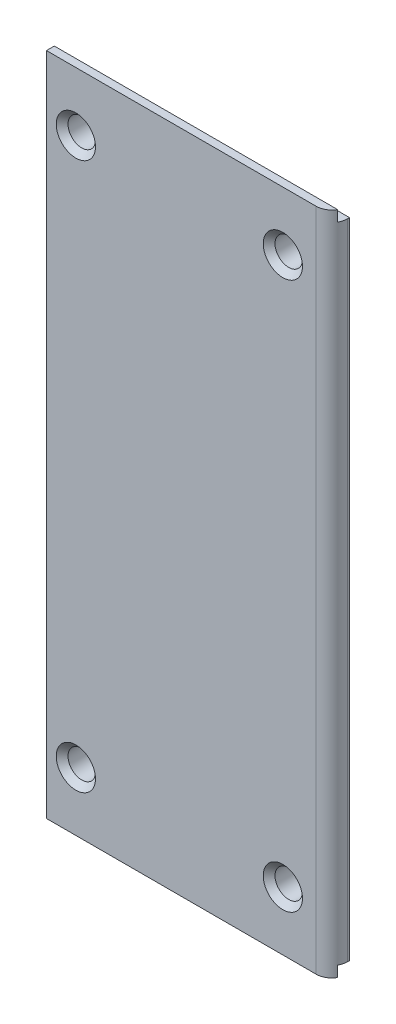
SolidWorks part; units mm, degrees
ref_plane "Спереди" through (0, 0, 0) normal (0, 0, 1) x (1, 0, 0)
ref_plane "Сверху" through (0, 0, 0) normal (0, 1, 0) x (1, 0, 0)
ref_plane "Справа" through (0, 0, 0) normal (1, 0, 0) x (0, 0, -1)
sketch "Эскиз1" plane through (0, 0, 0) normal (0, 0, 1) x (1, 0, 0)
  line L0 (-14.55, 33) -> (14.55, 33)
  line L1 (14.55, 33) -> (14.55, 34.1)
  line L2 (14.55, 34.1) -> (-14.55, 34.1)
  line L3 (-14.55, 34.1) -> (-14.55, 33)
  line L4 (14.55, -33) -> (-14.55, -33)
  line L5 (-14.55, -33) -> (-14.55, -34.1)
  line L6 (-14.55, -34.1) -> (14.55, -34.1)
  line L7 (14.55, -34.1) -> (14.55, -33)
sketch "Эскиз2" plane through (0, 0, 0) normal (0, 0, 1) x (1, 0, 0)
  line L0 (-14.55, 34.1) -> (-14.55, 33) construction
  line L1 (-14.55, 33.9) -> (14.55, 33.9)
  line L2 (-14.55, 33.9) -> (-14.55, -33.9)
  line L3 (-14.55, -33.9) -> (14.55, -33.9)
  line L4 (14.55, 33.9) -> (14.55, -33.9)
  line L5 (14.55, -34.1) -> (14.55, -33) construction
  line L6 (-14.55, -34.1) -> (14.55, -34.1) construction
  line L7 (14.55, 34.1) -> (-14.55, 34.1) construction
  dimension "D1" = 0.2
  dimension "D2" = 0.2
extrude "Бобышка-Вытянуть1" add sketch "Эскиз2" along normal blind 0.8
sketch "Эскиз3" plane through (0, 0, 0) normal (0, 0, -1) x (-1, 0, 0)
  line L0 (-14.55, -33.9) -> (-14.55, 33.9) construction
  line L1 (14.55, 33.9) -> (14.55, -33.9) construction
  line L2 (-14.55, 32.8) -> (14.55, 32.8)
  line L3 (-14.55, 32.8) -> (-14.55, -32.8)
  line L4 (-14.55, -32.8) -> (14.55, -32.8)
  line L5 (14.55, 32.8) -> (14.55, -32.8)
  line L6 (-14.55, -33) -> (14.55, -33) construction
  line L7 (14.55, 33) -> (-14.55, 33) construction
  dimension "D1" = 0.2
  dimension "D2" = 0.2
extrude "Бобышка-Вытянуть2" add sketch "Эскиз3" along normal blind 1
sketch "Эскиз4" plane through (0, 0, 0.8) normal (0, 0, 1) x (1, 0, 0)
  line L0 (14.55, 33.9) -> (-14.55, 33.9) construction
  line L1 (14.55, -33.9) -> (14.55, 33.9) construction
  line L2 (-14.55, 33.9) -> (-14.55, -33.9) construction
  line L3 (-14.55, -33.9) -> (14.55, -33.9) construction
  circle A0 centre (-11.55, 27.9) radius 1.4
  circle A1 centre (9.55, 27.9) radius 1.4
  circle A2 centre (9.55, -27.9) radius 1.4
  circle A3 centre (-11.55, -27.9) radius 1.4
  dimension "D1" = 2.8
  dimension "D2" = 6
  dimension "D3" = 6
  dimension "D4" = 5
  dimension "D5" = 3
  dimension "D6" = 5
  dimension "D7" = 6
  dimension "D8" = 6
  dimension "D9" = 3
extrude "Вырез-Вытянуть1" cut sketch "Эскиз4" against normal through all
chamfer "Фаска1" distance 0.6 angle 45 4 edges at (-10.15, -27.9, 0.8) (10.95, -27.9, 0.8) (-10.15, 27.9, 0.8) (10.95, 27.9, 0.8)
sketch "Эскиз5" plane through (0, 0, -1) normal (0, 0, -1) x (-1, 0, 0)
  line L0 (14.55, 32.8) -> (-14.55, 32.8) construction
  line L1 (-12.45, 32.8) -> (-11.45, 32.8)
  line L2 (-12.45, 32.8) -> (-12.45, -32.8)
  line L3 (-12.45, -32.8) -> (-11.45, -32.8)
  line L4 (-11.45, 32.8) -> (-11.45, -32.8)
  line L5 (-14.55, -32.8) -> (14.55, -32.8) construction
  line L6 (-14.55, 32.8) -> (-14.55, -32.8) construction
  dimension "D1" = 1
  dimension "D2" = 2.1
extrude "Бобышка-Вытянуть3" add sketch "Эскиз5" along normal blind 1
chamfer "Фаска2" distance 1 angle 45 1 edges at (11.45, 0, -1)
sketch "Эскиз6" plane through (0, 0, -1) normal (0, 0, -1) x (-1, 0, 0)
  arc A0 (-10.45, 28.9724) -> (-10.45, 26.8276) centre (-9.55, 27.9) ccw construction
  arc A1 (-10.45, 26.8276) -> (-10.45, 28.9724) centre (-9.55, 27.9) ccw construction
  arc A2 (-10.45, 28.9724) -> (-10.45, 26.8276) centre (-9.55, 27.9) ccw
  arc A3 (-10.45, 26.8276) -> (-10.45, 28.9724) centre (-9.55, 27.9) ccw
  circle A4 centre (11.55, 27.9) radius 1.4 construction
  circle A5 centre (11.55, 27.9) radius 1.4
  circle A6 centre (11.55, -27.9) radius 1.4 construction
  circle A7 centre (11.55, -27.9) radius 1.4
  arc A8 (-10.45, -26.8276) -> (-10.45, -28.9724) centre (-9.55, -27.9) ccw construction
  arc A9 (-10.45, -28.9724) -> (-10.45, -26.8276) centre (-9.55, -27.9) ccw construction
  arc A10 (-10.45, -26.8276) -> (-10.45, -28.9724) centre (-9.55, -27.9) ccw
  arc A11 (-10.45, -28.9724) -> (-10.45, -26.8276) centre (-9.55, -27.9) ccw
extrude "Вытянуть-Тонкостенный1" add sketch "Эскиз6" along normal blind 1 thin thin type one direction wall 1
chamfer "Фаска3" distance 1 angle 45 2 edges at (11.95, -32.8, -2) (11.95, 32.8, -2)
fillet "Скругление1" radius 1.6 1 edges at (14.55, 0, 0.8)
